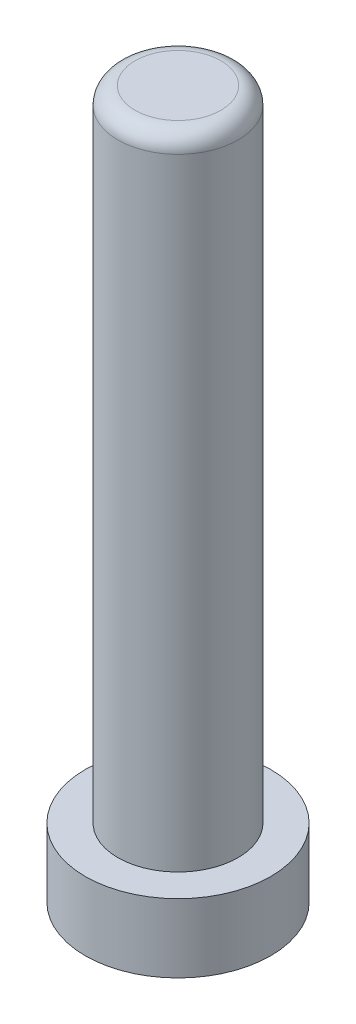
SolidWorks part; units mm, degrees
ref_plane "Front Plane" through (0, 0, 0) normal (0, 0, 1) x (1, 0, 0)
ref_plane "Top Plane" through (0, 0, 0) normal (0, 1, 0) x (1, 0, 0)
ref_plane "Right Plane" through (0, 0, 0) normal (1, 0, 0) x (0, 0, -1)
sketch "Sketch1" plane through (0, 0, 0) normal (0, 1, 0) x (1, 0, 0)
  line L1 (-2.8, -2.7) -> (2.8, -2.7) construction
  line L2 (-2.8, -2.7) -> (-2.8, 2.7) construction
  line L3 (-2.8, 2.7) -> (2.8, 2.7) construction
  line L4 (2.8, -2.7) -> (2.8, 2.7) construction
  line L5 (-2.8, -2.7) -> (2.8, 2.7) construction
  line L6 (-2.8, 2.7) -> (2.8, -2.7) construction
  circle A0 centre (0, 0) radius 2.7
  point P0 (0, 0)
  dimension "D1" = 5.6
  dimension "D2" = 5.4
extrude "Boss-Extrude1" add sketch "Sketch1" along normal blind 2
sketch "Sketch2" plane through (0, 2, 0) normal (0, 1, 0) x (1, 0, 0)
  circle A0 centre (0, 0) radius 1.75
  dimension "D1" = 3.5
sketch "Sketch3" plane through (0, 0, 0) normal (0, -1, 0) x (1, 0, 0)
  circle A0 centre (0, 0) radius 1.2
  circle A1 centre (0, 0) radius 0.95
  point P0 (0, 0)
  dimension "D1" = 2.4
  dimension "D2" = 1.9
extrude "Cut-Extrude2" cut sketch "Sketch3" against normal blind 9.5 contours A1
extrude "Boss-Extrude2" add sketch "Sketch2" along normal blind 18.6
sketch "Sketch7" plane through (0, 0, 0) normal (0, -1, 0) x (1, 0, 0)
  circle A0 centre (0, 0) radius 1.2
  dimension "D1" = 2.4
extrude "Cut-Extrude4" cut sketch "Sketch7" against normal blind 2.8
fillet "Fillet2" radius 0.5 1 edges at (0, 20.6, 1.75)
sketch "Sketch8" plane through (0, 0, 0) normal (0, -1, 0) x (1, 0, 0)
  circle A0 centre (0, 0) radius 0.95
  dimension "D1" = 1.9
extrude "Cut-Extrude5" cut sketch "Sketch8" against normal blind 10.5
